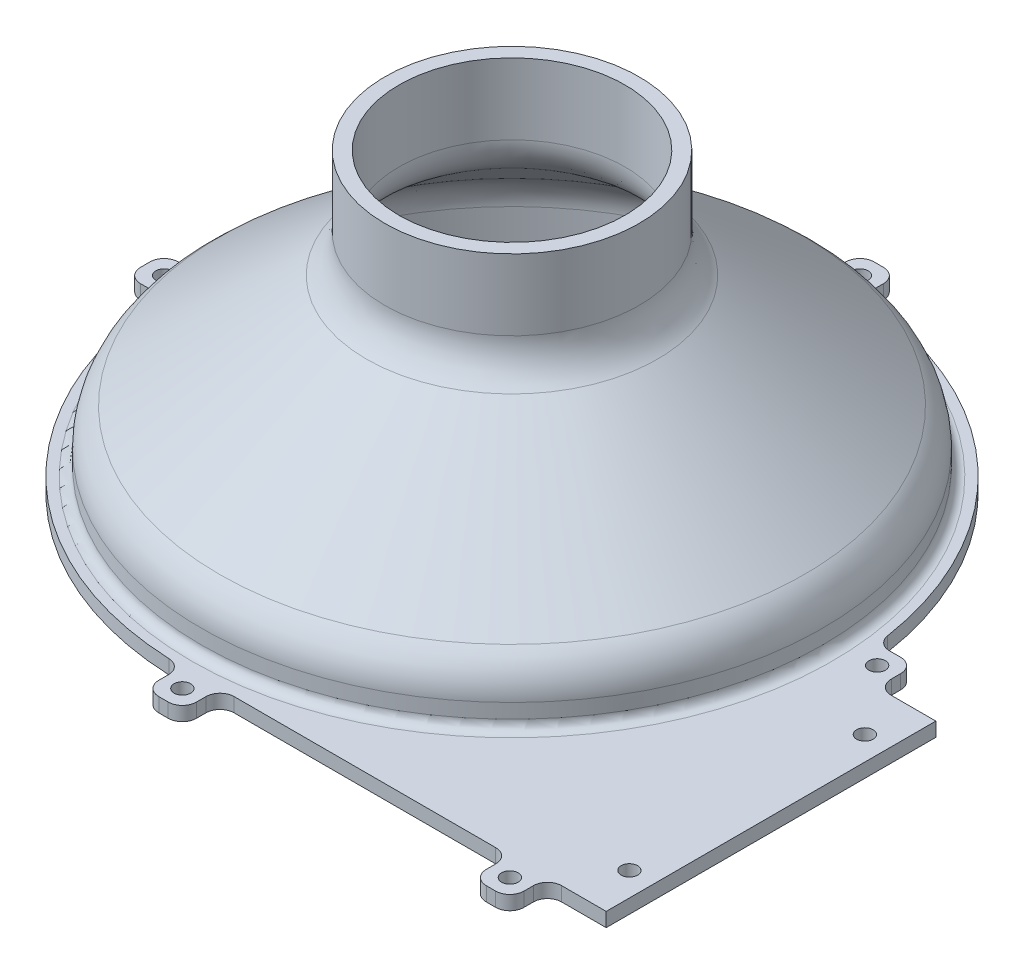
SolidWorks part; units mm, degrees
ref_plane "Front Plane" through (0, 0, 0) normal (0, 0, 1) x (1, 0, 0)
ref_plane "Top Plane" through (0, 0, 0) normal (0, 1, 0) x (1, 0, 0)
ref_plane "Right Plane" through (0, 0, 0) normal (1, 0, 0) x (0, 0, -1)
sketch "Sketch2" plane through (0, 0, 0) normal (0, 1, 0) x (1, 0, 0)
  line L0 (70, 0) -> (70, -70) construction
  line L1 (0, -70) -> (90, -70)
  line L3 (70, 0) -> (90, 0)
  line L4 (90, -70) -> (90, 0)
  arc A0 (70, 0) -> (0, -70) centre (0, 0) ccw
  circle A1 centre (0, 0) radius 63
  dimension "D1" = 140
  dimension "D4" = 126
  dimension "D3" = 20
extrude "Boss-Extrude1" add sketch "Sketch2" along normal blind 3
sketch "Sketch3" plane through (0, 3, 0) normal (0, 1, 0) x (1, 0, 0)
  circle A2 centre (0, 0) radius 63 construction
  circle A3 centre (0, 0) radius 63
  circle A4 centre (0, 0) radius 66
  dimension "D1" = 3
extrude "Boss-Extrude2" add sketch "Sketch3" along normal blind 10
sketch "Sketch6" plane through (0, 0, 0) normal (1, 0, 0) x (0, 0, -1)
  line L0 (-66, 13) -> (-27, 43)
  line L1 (-27, 43) -> (-24, 43)
  line L2 (-24, 43) -> (-63, 13)
  line L3 (66, 13) -> (-66, 13) construction
  line L4 (-66, 13) -> (-63, 13)
  line L5 (0, 0) -> (0, 43) construction
  line L6 (-70, 0) -> (70, 0) construction
  line L7 (-24, 43) -> (0, 43) construction
  dimension "D1" = 3
  dimension "D2" = 30
  dimension "D3" = 27
revolve "Revolve1" add sketch "Sketch6" angle 360 about L5
sketch "Sketch7" plane through (0, 43, 0) normal (0, 1, 0) x (1, 0, 0)
  circle A0 centre (0, 0) radius 27
  circle A1 centre (0, 0) radius 24
  circle A2 centre (0, 0) radius 24 construction
  circle A3 centre (0, 0) radius 27 construction
extrude "Boss-Extrude3" add sketch "Sketch7" along normal blind 20
fillet "Fillet1" radius 10 4 edges at (0, 43, -24) (0, 13, -63) (0, 13, 66) (0, 43, 27)
fillet "Fillet2" radius 2 1 edges at (0, 3, 66)
sketch "Sketch8" plane through (0, 0, 0) normal (0, -1, 0) x (1, 0, 0)
  line L21 (90, 0) -> (70, 0) construction
  line L22 (77.5414, 0) -> (69.5414, 0)
  line L23 (77.5414, 0) -> (77.5414, -8)
  line L24 (77.5414, -8) -> (69.5414, -8)
  line L25 (69.5414, 0) -> (69.5414, -8)
  line L26 (73.5414, 0) -> (73.5414, -8) construction
  line L27 (0, 70) -> (90, 70) construction
  line L28 (77.5414, 70) -> (69.5414, 70)
  line L29 (77.5414, 70) -> (77.5414, 78)
  line L30 (77.5414, 78) -> (69.5414, 78)
  line L31 (69.5414, 70) -> (69.5414, 78)
  line L32 (73.5414, 78) -> (73.5414, 70) construction
  line L33 (-73.8856, 4) -> (-73.8856, -4) construction
  line L34 (-69.8856, 4) -> (-77.8856, 4)
  line L35 (-69.8856, 4) -> (-69.8856, -4)
  line L36 (-69.8856, -4) -> (-77.8856, -4)
  line L37 (-77.8856, 4) -> (-77.8856, -4)
  line L38 (0, -69.8856) -> (0, -77.8856) construction
  line L39 (-4, -69.8856) -> (4, -69.8856)
  line L40 (-4, -69.8856) -> (-4, -77.8856)
  line L41 (-4, -77.8856) -> (4, -77.8856)
  line L42 (4, -69.8856) -> (4, -77.8856)
  line L43 (4, 78) -> (4, 70) construction
  line L44 (0, 70) -> (8, 70)
  line L45 (0, 70) -> (0, 78)
  line L46 (0, 78) -> (8, 78)
  line L47 (8, 70) -> (8, 78)
  arc A23 (0, 70) -> (70, 0) centre (0, 0) ccw construction
  circle A24 centre (73.5414, -4) radius 1.75
  circle A25 centre (73.5414, 74) radius 1.75
  circle A26 centre (-73.8856, 0) radius 1.75
  circle A27 centre (0, -73.8856) radius 1.75
  circle A28 centre (4, 74) radius 1.75
  dimension "D3" = 3.5
  dimension "D5" = 3.5
  dimension "D8" = 3.5
  dimension "D11" = 3.5
  dimension "D13" = 3.5
  dimension "D1" = 8
  dimension "D2" = 8
  dimension "D4" = 8
  dimension "D6" = 8
  dimension "D7" = 8
  dimension "D9" = 8
  dimension "D10" = 8
  dimension "D12" = 8
extrude "Boss-Extrude4" add sketch "Sketch8" against normal up to surface (3 mm away) up to face at (0, 3, 68)
fillet "Fillet3" radius 3 19 edges at (77.5414, 1.5, 0) (69.5414, 1.5, -8) (77.5414, 1.5, -8) (77.5414, 1.5, 70) (77.5414, 1.5, 78) (69.5414, 1.5, 78) (69.5414, 1.5, 70) (8, 1.5, 70) (8, 1.5, 78) (0, 1.5, 78) (0, 1.5, 70) (-69.8856, 1.5, 4) (-77.8856, 1.5, 4) (-77.8856, 1.5, -4) (-69.8856, 1.5, -4) (-4, 1.5, -77.8856) (4, 1.5, -77.8856) (4, 1.5, -69.8856) (-4, 1.5, -69.8856)
sketch "Sketch9" plane through (0, 3, 0) normal (0, 1, 0) x (1, 0, 0)
  line L0 (84.93, 0) -> (84.93, -70) construction
  line L1 (90, 0) -> (80.5414, 0) construction
  line L2 (80.5414, -70) -> (90, -70) construction
  line L3 (90, -70) -> (90, 0) construction
  circle A0 centre (84.93, -10) radius 1.75
  circle A1 centre (84.93, -60) radius 1.75
  dimension "D2" = 3.5
  dimension "D3" = 3.5
  dimension "D1" = 5.07
  dimension "D4" = 10
  dimension "D5" = 10
extrude "Cut-Extrude1" cut sketch "Sketch9" against normal through all
equation "\"LoftHeight\"= 30"
